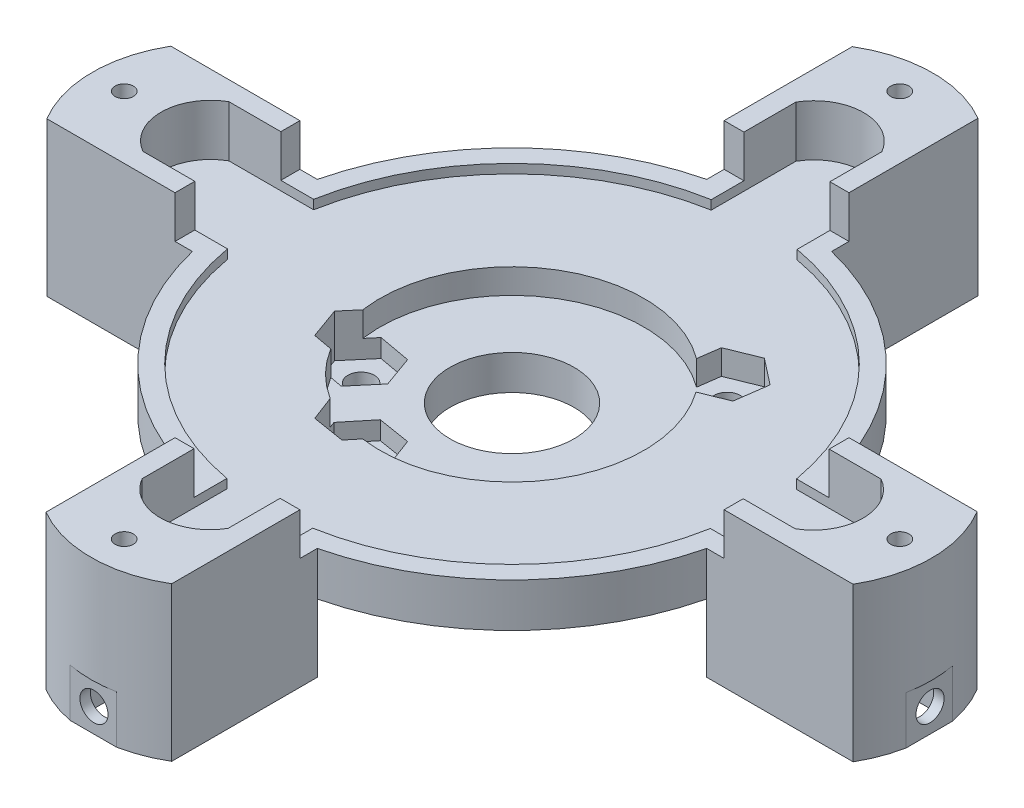
SolidWorks part; units mm, degrees
note: '?' marks a value the reader was unsure of. The reader was unsure of these and kept them because the rebuilt part matched: shared geometry of "Sketch5<3>".
ref_plane "Front Plane" through (0, 0, 0) normal (0, 0, 1) x (1, 0, 0)
ref_plane "Top Plane" through (0, 0, 0) normal (0, 1, 0) x (1, 0, 0)
ref_plane "Right Plane" through (0, 0, 0) normal (1, 0, 0) x (0, 0, -1)
sketch "Sketch1" plane through (0, 0, 0) normal (0, 1, 0) x (1, 0, 0)
  circle A0 centre (0, 0) radius 32
  dimension "D1" = 64
extrude "Boss-Extrude1" add sketch "Sketch1" along normal blind 8.3
sketch "Sketch6" plane through (0, 8.3, 0) normal (0, 1, 0) x (1, 0, 0)
  line L2 (-7.5498, 48.6966) -> (-7.5498, 31.0966)
  line L4 (7.5498, 48.8009) -> (7.5498, 31.0966)
  line L32 (-7.5498, 31.0966) -> (7.5498, 31.0966)
  line L33 (31.0966, 7.5498) -> (31.0966, -7.5498)
  line L34 (48.8009, -7.5498) -> (31.0966, -7.5498)
  line L35 (48.6966, 7.5498) -> (31.0966, 7.5498)
  line L36 (7.5498, -31.0966) -> (-7.5498, -31.0966)
  line L37 (-7.5498, -48.8009) -> (-7.5498, -31.0966)
  line L38 (7.5498, -48.6966) -> (7.5498, -31.0966)
  line L39 (-31.0966, -7.5498) -> (-31.0966, 7.5498)
  line L40 (-48.8009, 7.5498) -> (-31.0966, 7.5498)
  line L41 (-48.6966, -7.5498) -> (-31.0966, -7.5498)
  circle A1 centre (0, 0) radius 32 construction
  arc A2 (7.5498, 48.8009) -> (-7.5498, 48.6966) centre (0.0879, 36.0196) ccw
  arc A12 (48.8009, -7.5498) -> (48.6966, 7.5498) centre (36.0196, -0.0879) ccw
  arc A13 (-7.5498, -48.8009) -> (7.5498, -48.6966) centre (-0.0879, -36.0196) ccw
  arc A14 (-48.8009, 7.5498) -> (-48.6966, -7.5498) centre (-36.0196, 0.0879) ccw
  point P10 (-7.5498, 31.0966)
  point P27 (0, 0)
  dimension "D4" = 29.6
  dimension "D1" = 17.6
  dimension "D2" = 15.1
  dimension "D3" = 4
  dimension "D5" = 31.0966
  dimension "D6" = 31.0966
extrude "Boss-Extrude2" add sketch "Sketch6" along normal blind 5.1 and the other way blind 13.5
sketch "Sketch2" plane through (0, 8.3, 0) normal (0, 1, 0) x (1, 0, 0)
  line L0 (29.2334, -5.2441) -> (39.4793, -5.2441)
  line L2 (5.2441, 29.2334) -> (5.2441, 39.4793)
  line L4 (-5.1559, 29.2491) -> (-5.1559, 39.4793)
  line L5 (0.0441, 42.486) -> (0.0441, 57.8574) construction
  line L6 (29.2491, 5.1559) -> (39.4793, 5.1559)
  line L7 (-5.2441, -29.2334) -> (-5.2441, -39.4793)
  line L8 (5.1559, -29.2491) -> (5.1559, -39.4793)
  line L9 (-29.2334, 5.2441) -> (-39.4793, 5.2441)
  line L10 (-29.2491, -5.1559) -> (-39.4793, -5.1559)
  arc A0 (-5.1559, 29.2491) -> (-29.2334, 5.2441) centre (0, 0) ccw
  arc A1 (5.2441, 39.4793) -> (-5.1559, 39.4793) centre (0.0441, 36.486) ccw
  arc A2 (39.4793, -5.2441) -> (39.4793, 5.1559) centre (36.486, -0.0441) ccw
  arc A3 (-5.2441, -39.4793) -> (5.1559, -39.4793) centre (-0.0441, -36.486) ccw
  arc A4 (-39.4793, 5.2441) -> (-39.4793, -5.1559) centre (-36.486, 0.0441) ccw
  arc A5 (-29.2491, -5.1559) -> (-5.2441, -29.2334) centre (0, 0) ccw
  arc A6 (29.2491, 5.1559) -> (5.2441, 29.2334) centre (0, 0) ccw
  arc A7 (5.1559, -29.2491) -> (29.2334, -5.2441) centre (0, 0) ccw
  point P7 (-5.1559, 29.2491)
  point P28 (0, 0)
  dimension "D1" = 59.4
  dimension "D5" = 12
  dimension "D2" = 4
  dimension "D3" = 10.4
extrude "Cut-Extrude1" cut sketch "Sketch2" against normal blind 1.1 and the other way up to next
sketch "Sketch3" plane through (0, 7.2, 0) normal (0, 1, 0) x (1, 0, 0)
  circle A0 centre (0, 0) radius 15.95
  dimension "D1" = 31.9
extrude "Cut-Extrude2" cut sketch "Sketch3" against normal blind 3
sketch "Sketch4" plane through (0, 4.2, 0) normal (0, 1, 0) x (1, 0, 0)
  circle A0 centre (0, 0) radius 7.5
  dimension "D1" = 15
extrude "Cut-Extrude3" cut sketch "Sketch4" against normal up to next
sketch "Sketch5" plane through (0, 0, 0) normal (0, -1, 0) x (1, 0, 0)
  line L0 (-19.75, 19.75) -> (19.75, -19.75) construction
  line L1 (-19.75, 19.75) -> (19.75, 19.75)
  line L2 (-19.75, 19.75) -> (-19.75, -19.75)
  line L3 (-19.75, -19.75) -> (19.75, -19.75)
  line L4 (19.75, 19.75) -> (19.75, -19.75)
  line L5 (0, 0) -> (0, -19.75) construction
  line L6 (0, 0) -> (19.75, 0) construction
  line L7 (0, 0) -> (13.0108, -13.0108) construction
  line L8 (0, 0) -> (0, 19.75) construction
  line L9 (0, 0) -> (-19.75, 0) construction
  line L10 (0, 0) -> (-19.75, -19.75) construction
  line L11 (0, 0) -> (11.7564, -11.7564) construction
  circle A0 centre (0, 0) radius 20.3
  circle A1 centre (13.0108, -13.0108) radius 1.6
  circle A2 centre (11.7564, -11.7564) radius 6
  circle A3 centre (0, 0) radius 18.4 construction
  circle A4 centre (-4.8083, 13.435) radius 1.6
  circle A5 centre (-13.435, 4.8083) radius 1.6
  circle A7 centre (0, 0) radius 32
  dimension "D1" = 40.6
  dimension "D3" = 3.2
  dimension "D4" = 12
  dimension "D8" = 3.2
  dimension "D9" = 3.2
  dimension "D12" = 36.8
  dimension "D7" = 64
  dimension "D2" = 39.5
  dimension "D5" = 12.9
  dimension "D6" = 12.9
  dimension "D10" = 6.1
  dimension "D11" = 6.1
extrude "Cut-Extrude4" cut sketch "Sketch5" against normal blind 3
extrude "Cut-Extrude5" cut sketch "Sketch5<3>" against normal up to next contours A1 | A5 | A4
sketch "Sketch5<3>" plane through (0, 0, 0) normal (0, -1, 0) x (1, 0, 0) same geometry as "Sketch5"
sketch "Sketch7" plane through (0, 7.2, 0) normal (0, 1, 0) x (1, 0, 0)
  line L1 (9.8683, 15.4592) -> (9.3191, 11.5135)
  line L2 (9.3191, 11.5135) -> (12.4616, 9.0651)
  line L3 (12.4616, 9.0651) -> (16.1532, 10.5623)
  line L4 (16.1532, 10.5623) -> (16.7024, 14.508)
  line L5 (16.7024, 14.508) -> (13.5599, 16.9564)
  line L6 (13.5599, 16.9564) -> (9.8683, 15.4592)
  circle A0 centre (13.0108, 13.0108) radius 3.45 construction
  circle A2 centre (0, 0) radius 7.5 construction
  dimension "D1" = 6.9
  dimension "D2" = 19.3
extrude "Cut-Extrude6" cut sketch "Sketch7" against normal up to surface (3 mm away) up to face at (-13.435, 4.2, 6.4083)
sketch "Sketch9" plane through (0, 4.2, 0) normal (0, 1, 0) x (1, 0, 0)
  line L1 (-6.2195, -9.7096) -> (-8.7402, -12.7945)
  line L2 (-8.7402, -12.7945) -> (-7.329, -16.5199)
  line L3 (-7.329, -16.5199) -> (-3.3971, -17.1604)
  line L4 (-3.3971, -17.1604) -> (-0.8764, -14.0756)
  line L5 (-0.8764, -14.0756) -> (-2.2876, -10.3502)
  line L6 (-2.2876, -10.3502) -> (-6.2195, -9.7096)
  line L7 (-10.8596, -1.7691) -> (-14.7794, -1.0583)
  line L8 (-14.7794, -1.0583) -> (-17.3548, -4.0976)
  line L9 (-17.3548, -4.0976) -> (-16.0105, -7.8476)
  line L10 (-16.0105, -7.8476) -> (-12.0907, -8.5584)
  line L11 (-12.0907, -8.5584) -> (-9.5152, -5.5191)
  line L12 (-9.5152, -5.5191) -> (-10.8596, -1.7691)
  circle A0 centre (-4.8083, -13.435) radius 3.45 construction
  circle A1 centre (-13.435, -4.8083) radius 3.45 construction
  circle A2 centre (0, 0) radius 7.5 construction
  dimension "D1" = 11
  dimension "D2" = 10.6
  dimension "D3" = 6.9
  dimension "D4" = 6.9
extrude "Cut-Extrude7" cut sketch "Sketch9" against normal blind 2.2 and the other way up to surface
sketch "Sketch10" plane through (0, 8.3, 0) normal (0, 1, 0) x (1, 0, 0)
  line L0 (0, 0) -> (-39.9223, 0) construction
  line L1 (-33.2, 33.2) -> (33.2, 33.2)
  line L2 (-33.2, 33.2) -> (-33.2, -33.2)
  line L3 (-33.2, -33.2) -> (33.2, -33.2)
  line L4 (33.2, 33.2) -> (33.2, -33.2)
  line L5 (0, 0) -> (0, 46.1219) construction
  dimension "D1" = 66.4
  dimension "D2" = 33.2
  dimension "D3" = 33.2
extrude "Cut-Extrude8" cut sketch "Sketch10" along normal up to next
sketch "Sketch11" plane through (0, 13.4, 0) normal (0, 1, 0) x (1, 0, 0)
  line L0 (-7.5498, -31.0966) -> (-7.5498, -48.8009) construction
  line L1 (-48.6966, -7.5498) -> (-31.0966, -7.5498) construction
  line L2 (-7.5498, 48.6966) -> (-7.5498, 31.0966) construction
  line L3 (31.0966, -7.5498) -> (48.8009, -7.5498) construction
  line L4 (-31.0966, -7.5498) -> (-31.0966, 7.5498) construction
  line L6 (-7.5498, 31.0966) -> (7.5498, 31.0966) construction
  line L7 (31.0966, 7.5498) -> (31.0966, -7.5498) construction
  line L8 (7.5498, -31.0966) -> (-7.5498, -31.0966) construction
  circle A3 centre (0.0002, -46.8966) radius 1.1
  circle A8 centre (-46.8966, 0.0002) radius 1.1
  circle A9 centre (0.0002, 46.8966) radius 1.1
  circle A10 centre (46.8966, 0.0002) radius 1.1
  dimension "D2" = 2.2
  dimension "D4" = 2.2
  dimension "D5" = 2.2
  dimension "D6" = 2.2
  dimension "D1" = 7.55
  dimension "D3" = 7.55
  dimension "D7" = 7.55
  dimension "D8" = 7.55
  dimension "D9" = 15.8
  dimension "D10" = 15.8
  dimension "D11" = 15.8
  dimension "D12" = 15.8
extrude "Cut-Extrude9" cut sketch "Sketch11" against normal up to next
sketch "Sketch12" plane through (0, -5.2, 0) normal (0, -1, 0) x (1, 0, 0)
  line L0 (49.2966, -2.6752) -> (44.4966, 2.6748) construction
  line L1 (-49.2966, -2.6502) -> (-44.4966, -2.6502)
  line L2 (-49.2966, -2.6502) -> (-49.2966, 2.6498)
  line L3 (-49.2966, 2.6498) -> (-44.4966, 2.6498)
  line L4 (-44.4966, -2.6502) -> (-44.4966, 2.6498)
  line L5 (-49.2966, -2.6502) -> (-44.4966, 2.6498) construction
  line L6 (-2.6748, -44.4966) -> (2.6752, -49.2966) construction
  line L7 (-2.6748, -44.4966) -> (2.6752, -44.4966)
  line L8 (2.6752, 44.4966) -> (-2.6748, 44.4966)
  line L9 (2.6752, 44.4966) -> (2.6752, 49.2966)
  line L10 (2.6752, 49.2966) -> (-2.6748, 49.2966)
  line L11 (-2.6748, 44.4966) -> (-2.6748, 49.2966)
  line L12 (49.2966, 2.6748) -> (49.2966, -2.6752)
  line L13 (49.2966, 2.6748) -> (44.4966, 2.6748)
  line L14 (44.4966, 2.6748) -> (44.4966, -2.6752)
  line L15 (49.2966, -2.6752) -> (44.4966, -2.6752)
  line L20 (49.2966, 2.6748) -> (44.4966, -2.6752) construction
  line L21 (-2.6748, -44.4966) -> (-2.6748, -49.2966)
  line L22 (-2.6748, -49.2966) -> (2.6752, -49.2966)
  line L23 (-2.6748, 44.4966) -> (2.6752, 49.2966) construction
  line L24 (-2.6748, 49.2966) -> (2.6752, 44.4966) construction
  line L25 (2.6752, -44.4966) -> (2.6752, -49.2966)
  line L26 (2.6752, -44.4966) -> (-2.6748, -49.2966) construction
  line L27 (-48.6966, 7.5498) -> (-31.0966, 7.5498) construction
  line L29 (-7.5498, -48.6966) -> (-7.5498, -31.0966) construction
  line L30 (31.0966, 7.5498) -> (48.8009, 7.5498) construction
  line L31 (-7.5498, 31.0966) -> (-7.5498, 48.8009) construction
  circle A0 centre (46.8966, -0.0002) radius 1.1 construction
  circle A2 centre (-46.8966, -0.0002) radius 1.1 construction
  circle A3 centre (0.0002, 46.8966) radius 1.1 construction
  circle A4 centre (0.0002, -46.8966) radius 1.1 construction
  point P5 (0.0002, 46.8966)
  point P8 (-46.8966, -0.0002)
  point P9 (46.8966, -0.0002)
  point P24 (0.2267, 0.217)
  point P26 (0.0002, -46.8966)
  dimension "D4" = 4.8
  dimension "D5" = 0
  dimension "D7" = 0
  dimension "D1" = 0
  dimension "D2" = 5.3
  dimension "D3" = 4.8
  dimension "D6" = 0
  dimension "D8" = 5.35
  dimension "D9" = 5.35
  dimension "D10" = 4.8
  dimension "D11" = 4.8
  dimension "D12" = 5.35
  dimension "D13" = 7.55
  dimension "D14" = 7.55
  dimension "D15" = 7.55
  dimension "D16" = 7.55
extrude "Cut-Extrude10" cut sketch "Sketch12" against normal blind 12.6
sketch "Sketch13" plane through (0, -5.2, 0) normal (0, -1, 0) x (1, 0, 0)
  line L0 (7.5498, 31.0966) -> (-7.5498, 31.0966) construction
  line L1 (-3.1498, 42.0966) -> (3.1502, 42.0966)
  line L2 (-3.1498, 42.0966) -> (-3.1498, 39.5966)
  line L3 (-3.1498, 39.5966) -> (3.1502, 39.5966)
  line L4 (3.1502, 42.0966) -> (3.1502, 39.5966)
  line L5 (-7.5498, -31.0966) -> (7.5498, -31.0966) construction
  line L6 (-7.5498, -48.6966) -> (-7.5498, -31.0966) construction
  line L7 (-31.0966, -7.5498) -> (-48.8009, -7.5498) construction
  line L8 (42.0966, 3.1498) -> (39.5966, 3.1498)
  line L9 (42.0966, 3.1498) -> (42.0966, -3.1502)
  line L10 (42.0966, -3.1502) -> (39.5966, -3.1502)
  line L11 (39.5966, 3.1498) -> (39.5966, -3.1502)
  line L12 (3.1998, -42.0961) -> (3.1502, -39.5966)
  line L13 (3.1998, -42.0961) -> (-3.1002, -42.0961)
  line L14 (-3.1002, -42.0961) -> (-3.1498, -39.5966)
  line L15 (3.1502, -39.5966) -> (-3.1498, -39.5966)
  line L16 (-42.0966, -3.1498) -> (-39.5966, -3.1502)
  line L17 (-42.0966, -3.1498) -> (-42.0966, 3.1502)
  line L18 (-42.0966, 3.1502) -> (-39.5966, 3.1498)
  line L19 (-39.5966, -3.1502) -> (-39.5966, 3.1498)
  line L20 (7.5498, -31.0966) -> (7.5498, -48.8009) construction
  line L21 (-31.0966, 7.5498) -> (-31.0966, -7.5498) construction
  line L23 (-48.6966, 7.5498) -> (-31.0966, 7.5498) construction
  line L24 (31.0966, -7.5498) -> (31.0966, 7.5498) construction
  line L25 (31.0966, 7.5498) -> (48.8009, 7.5498) construction
  point P6 (-39.5966, -0.0002)
  point P27 (0.5002, 0.4998)
  point P29 (42.0966, -0.0002)
  point P31 (0.0002, -39.5966)
  point P34 (39.5966, -0.0002)
  point P35 (-42.0966, 0.0002)
  point P38 (0.0498, -42.0961)
  dimension "D1" = 6.3
  dimension "D2" = 2.5
  dimension "D3" = 8.5
  dimension "D4" = 2.5
  dimension "D6" = 8.5
  dimension "D7" = 8.5
  dimension "D8" = 6.3
  dimension "D5" = 7.55
  dimension "D9" = 6.3
  dimension "D10" = 2.5
  dimension "D11" = 7.55
  dimension "D12" = 8.5
  dimension "D13" = 7.55
  dimension "D14" = 7.55
  dimension "D15" = 6.3
  dimension "D16" = 2.5
  dimension "D17" = 6.3
  dimension "D18" = 7.55
  dimension "D19" = 6.3
  dimension "D20" = 6.3
  dimension "D21" = 7.5
extrude "Cut-Extrude11" cut sketch "Sketch13" against normal blind 6.5
sketch "Sketch14" plane through (0, -5.2, 0) normal (0, -1, 0) x (1, 0, 0)
  line L0 (7.5498, 31.0966) -> (-7.5498, 31.0966) construction
  line L1 (-7.5498, 31.0966) -> (-7.5498, 48.8009) construction
  line L3 (-48.6966, 7.5498) -> (-31.0966, 7.5498) construction
  line L4 (-7.5498, -48.6966) -> (-7.5498, -31.0966) construction
  circle A0 centre (0.0002, 35.1966) radius 1.7
  circle A1 centre (35.197, -0.0002) radius 1.7
  circle A2 centre (0.0002, -35.197) radius 1.7
  circle A3 centre (-35.1966, -0.0002) radius 1.7
  point P16 (0.0002, -0.0002)
  dimension "D1" = 3.4
  dimension "D7" = 35.1968
  dimension "D2" = 4.1
  dimension "D3" = 7.55
  dimension "D4" = 7.55
  dimension "D5" = 7.55
  dimension "D6" = 4
  dimension "D8" = 35.1968
extrude "Cut-Extrude12" cut sketch "Sketch14" against normal blind 3.5
sketch "Sketch15" plane through (-31.0966, 0, 0) normal (1, 0, 0) x (0, 0, -1)
  line L0 (-7.5498, -5.2) -> (7.5498, -5.2) construction
  line L1 (-3.1498, -1.7) -> (3.1502, -1.7)
  line L2 (-3.1498, -1.7) -> (-3.1498, 0.8)
  line L3 (-3.1498, 0.8) -> (3.1502, 0.8)
  line L4 (3.1502, -1.7) -> (3.1502, 0.8)
  line L7 (-7.5498, -5.2) -> (-7.5498, 13.4) construction
  point P6 (0.0002, 0.8)
  dimension "D1" = 3.5
  dimension "D2" = 7.55
  dimension "D3" = 6.3
  dimension "D4" = 2.5
extrude "Cut-Extrude13" cut sketch "Sketch15" against normal blind 7.6
pattern_circular "CirPattern1" count 4 every 90 about axis through (0, 0, 0) along (0, 1, 0) of "Cut-Extrude13"
sketch "Sketch16" plane through (0, -5.2, 0) normal (0, -1, 0) x (1, 0, 0)
  line L0 (50.5524, 2.8879) -> (50.5524, -2.7121)
  line L2 (2.8879, -50.5524) -> (-2.7121, -50.5524)
  line L3 (-50.5524, -2.8879) -> (-50.5524, 2.7121)
  line L4 (-2.8879, 50.5524) -> (2.7121, 50.5524)
  arc A0 (48.6966, -7.5498) -> (48.8009, 7.5498) centre (36.0196, 0.0879) ccw construction
  arc A1 (50.5524, -2.7121) -> (50.5524, 2.8879) centre (36.0196, 0.0879) ccw
  arc A2 (-2.7121, -50.5524) -> (2.8879, -50.5524) centre (0.0879, -36.0196) ccw
  arc A3 (-50.5524, 2.7121) -> (-50.5524, -2.8879) centre (-36.0196, -0.0879) ccw
  arc A4 (2.7121, 50.5524) -> (-2.8879, 50.5524) centre (-0.0879, 36.0196) ccw
  arc A5 (-48.6966, 7.5498) -> (-48.8009, -7.5498) centre (-36.0196, -0.0879) ccw construction
  point P18 (0, 0)
  dimension "D1" = 5.6
  dimension "D2" = 4
extrude "Cut-Extrude14" cut sketch "Sketch16" against normal blind 5.8
sketch "Sketch17" plane through (50.5524, 0, 0) normal (1, 0, 0) x (0, 0, -1)
  line L1 (-2.8879, -5.2) -> (2.7121, -5.2) construction
  line L4 (-7.5498, -5.2) -> (-7.5498, 13.4) construction
  circle A0 centre (0.0002, -2.3) radius 1.7
  dimension "D1" = 3.4
  dimension "D2" = 7.55
  dimension "D3" = 2.9
extrude "Cut-Extrude15" cut sketch "Sketch17" against normal blind 9
ref_axis "Axis1" through (0, 0, 0) along (0, 1, 0)?
pattern_circular "CirPattern9" count 4 over 360 about axis through (0, 0, 0) along (0, 1, 0) of "Cut-Extrude15"
equation "\"D4@Sketch11\"=\"D2@Sketch11\""
equation "\"D5@Sketch11\"=\"D2@Sketch11\""
equation "\"D6@Sketch11\"=\"D2@Sketch11\""
